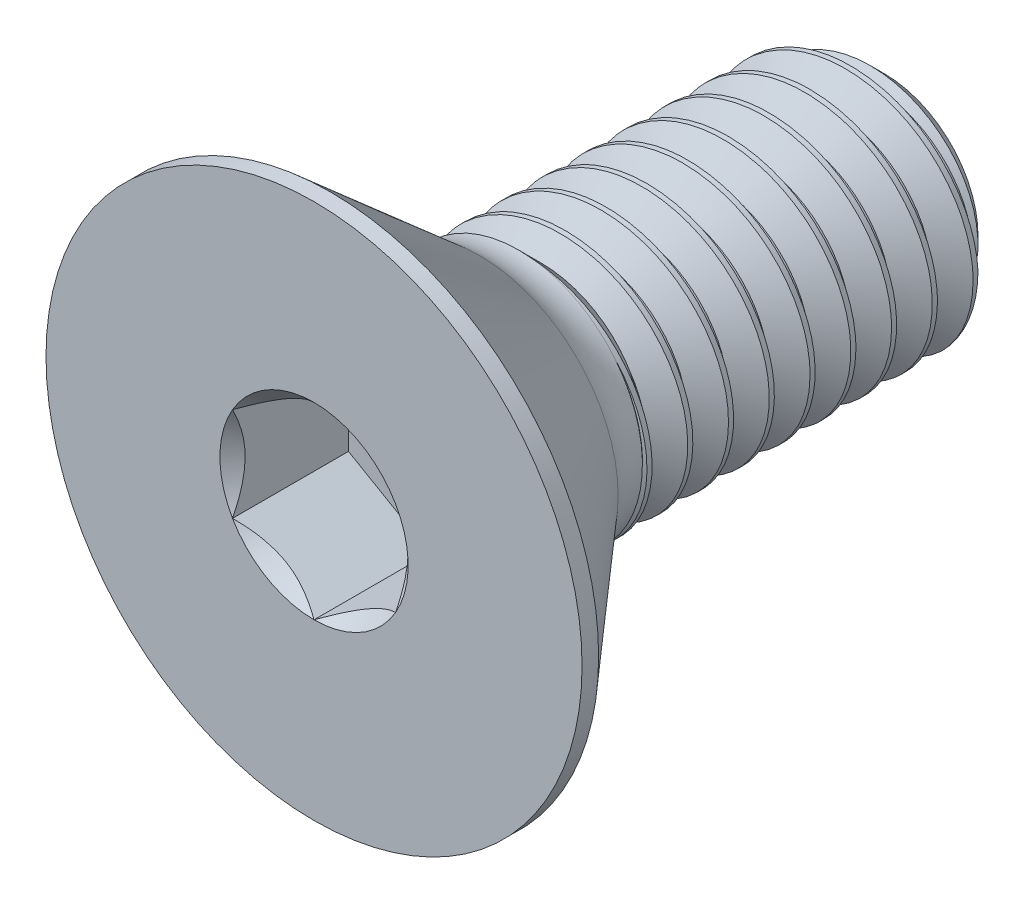
SolidWorks part; units mm, degrees
material "AISI 4340 Steel, normalized"
ref_plane "Front" through (0, 0, 0) normal (0, 0, 1) x (1, 0, 0)
ref_plane "Top" through (0, 0, 0) normal (0, 1, 0) x (1, 0, 0)
ref_plane "Right" through (0, 0, 0) normal (1, 0, 0) x (0, 0, -1)
sketch "Sketch1" plane through (0, 0, 0) normal (1, 0, 0) x (0, 0, -1)
  line L0 (0, 5.2197) -> (0.3226, 5.2197) construction
  line L1 (0.3226, 5.2197) -> (3.2258, 2.696) construction
  line L2 (0, 2.413) -> (11.1125, 2.413)
  line L3 (11.1125, 2.413) -> (11.1125, 0)
  line L4 (11.1125, 0) -> (0, 0)
  line L5 (0, 0) -> (0, 5.2197) construction
  line L6 (0, 5.2197) -> (0, -5.2197) construction
  line L7 (11.1125, 2.413) -> (11.1125, -2.413) construction
  line L8 (0, -5.2197) -> (0.3226, -5.2197) construction
  line L9 (0.3226, -5.2197) -> (3.2258, -2.696) construction
  line L11 (0, 2.413) -> (0, 0)
  line L12 (3.9826, 2.413) -> (3.9826, 0) construction
  arc A1 (3.2258, 2.696) -> (3.9826, 2.413) centre (3.9826, 3.5666) ccw construction
  dimension "D1" = 0.3226
  dimension "Head Ht" = 3.2258
  dimension "Head Dia" = 10.4394
  dimension "Dia" = 4.826
  dimension "Lg" = 11.1125
  dimension "Head Angle" = 82
revolve "Revolve1" add sketch "Sketch1" angle 360 mid plane about L4
sketch "Sketch3" plane through (0, 0, -11.1125) normal (0, 0, -1) x (-1, 0, 0)
  circle A0 centre (0, 0) radius 2.413
curve "Helix/Spiral1" pitch 0.7937 height 11.1125 radius 2.413 centre (0, 0, -11.1125) axis (0, 0, 1) start towards (0, 1, 0)
sketch "Sketch2" plane through (0, 0, 0) normal (1, 0, 0) x (0, 0, -1)
  line L0 (11.1125, 2.413) -> (11.807, 2.413)
  line L1 (11.807, 2.413) -> (11.5094, 1.8974)
  line L2 (11.5094, 1.8974) -> (11.4102, 1.8974)
  line L3 (11.4102, 1.8974) -> (11.1125, 2.413)
  line L4 (11.2613, 2.1552) -> (11.6582, 2.1552) construction
  dimension "D1" = 60
  dimension "D2" = 0.0992
  dimension "D3" = 0.3969
chamfer "Chamfer1" distance 0.5953 angle 45 1 edges at (0, 2.413, -11.1125)
sweep "Cut-Sweep1" cut profiles "Sketch2" path "Helix/Spiral1"
sketch "Sketch7" plane through (0, 0, 0) normal (1, 0, 0) x (0, 0, -1)
  line L0 (0, 5.2197) -> (0.3226, 5.2197) construction
  line L1 (0.3226, 5.2197) -> (3.2258, 2.696) construction
  line L2 (0, 5.2197) -> (0.3226, 5.2197)
  line L3 (0.3226, 5.2197) -> (3.2258, 2.696)
  line L4 (3.9826, 2.413) -> (3.9826, 0) construction
  line L5 (3.9826, 2.413) -> (3.9826, 0)
  line L7 (0, 0) -> (0, 5.2197) construction
  line L8 (0, 0) -> (0, 5.2197)
  line L9 (0, 0) -> (3.9826, 0)
  line L10 (5.7417, 0) -> (-5.7417, 0) construction
  arc A0 (3.2258, 2.696) -> (3.9826, 2.413) centre (3.9826, 3.5666) ccw construction
  arc A1 (3.2258, 2.696) -> (3.9826, 2.413) centre (3.9826, 3.5666) ccw
revolve "Revolve2" add sketch "Sketch7" angle 360 mid plane about L9
ref_plane "Plane1" through (0, 0, -3.9826) normal (0, 0, 1) x (1, 0, 0)
sketch "Sketch8" plane through (0, 0, -3.9826) normal (0, 0, 1) x (1, 0, 0)
  circle A0 centre (0, 0) radius 2.413
extrude "Boss-Extrude1" add sketch "Sketch8" against normal through all draft 45
sketch "Sketch11" [suppressed] plane through (0, 0, 0) normal (1, 0, 0) x (0, 0, -1)
  line L0 (4.4996, 0) -> (-4.4996, 0) construction
  line L1 (7.3025, 3.8989) -> (1.7272, 3.8989)
  line L2 (7.3025, 3.8989) -> (7.3025, -3.8989)
  line L3 (7.3025, -3.8989) -> (1.7272, -3.8989)
  line L4 (1.7272, 3.8989) -> (1.7272, -3.8989)
  line L5 (0, 3.8989) -> (0.1727, 3.8989) construction
  line L7 (4.7625, 1.7526) -> (4.7625, 0) construction
  point P4 (1.7272, 0)
  dimension "D1" = 2.54
extrude "Cut-Extrude4" [suppressed] cut sketch "Sketch11" against normal through all and the other way through all
combine bodies "Combine1" operation type add bodies to combine 117 114
sketch "Sketch5" plane through (0, 0, 0) normal (0, 0, 1) x (1, 0, 0)
  line L1 (1.5875, -0.9165) -> (1.5875, 0.9165)
  line L2 (1.5875, 0.9165) -> (0, 1.8331)
  line L3 (0, 1.8331) -> (-1.5875, 0.9165)
  line L4 (-1.5875, 0.9165) -> (-1.5875, -0.9165)
  line L5 (-1.5875, -0.9165) -> (0, -1.8331)
  line L6 (0, -1.8331) -> (1.5875, -0.9165)
  circle A0 centre (0, 0) radius 1.5875 construction
  dimension "Hex" = 3.175
extrude "Cut-Extrude2" cut sketch "Sketch5" against normal blind 2.2581
sketch "Sketch6" plane through (0, 0, 0) normal (0, 0, 1) x (1, 0, 0)
  circle A0 centre (0, 0) radius 1.8331
extrude "Cut-Extrude3" cut sketch "Sketch6" against normal blind 2.2581 draft 45
sketch "Sketch9" [suppressed] plane through (0, 0, -12.3809) normal (0, 0, 1) x (1, 0, 0)
  circle A1 centre (0, 0) radius 9.525
  circle A2 centre (0, 0) radius 9.525
  point P0 (0, 9.525)
  dimension "D1" = 0
extrude "Boss-Extrude2" [suppressed] add sketch "Sketch9" against normal offset from surface (44.7691 mm away) 44.45 up to face at (0, 1.8177, -11.1125)
sketch "Sketch10" plane through (0, 0, 0) normal (1, 0, 0) x (0, 0, -1)
  line L0 (11.1125, 2.413) -> (11.1125, -2.413) construction
  point P0 (9.9219, -2.413)
  dimension "D1" = 1.1906
equation "\"D3@Helix/Spiral1\" = \"Lg@Sketch1\""
equation "\"D2@Sketch2\" = \"D4@Helix/Spiral1\" * .125"
equation "\"D3@Sketch2\" = \"D4@Helix/Spiral1\" * .5"
equation "\"D1@Chamfer1\" = \"D4@Helix/Spiral1\" * .75"
equation "\"D1@Cut-Extrude2\" = \"Head Ht@Sketch1\" * .7"
equation "\"D1@Sketch1\" = \"Head Ht@Sketch1\" * .1"
equation "\"D1@Sketch10\" = \"D4@Helix/Spiral1\" * 1.5"
equation "\"D1@Cut-Extrude3\" = \"D1@Cut-Extrude2\""
